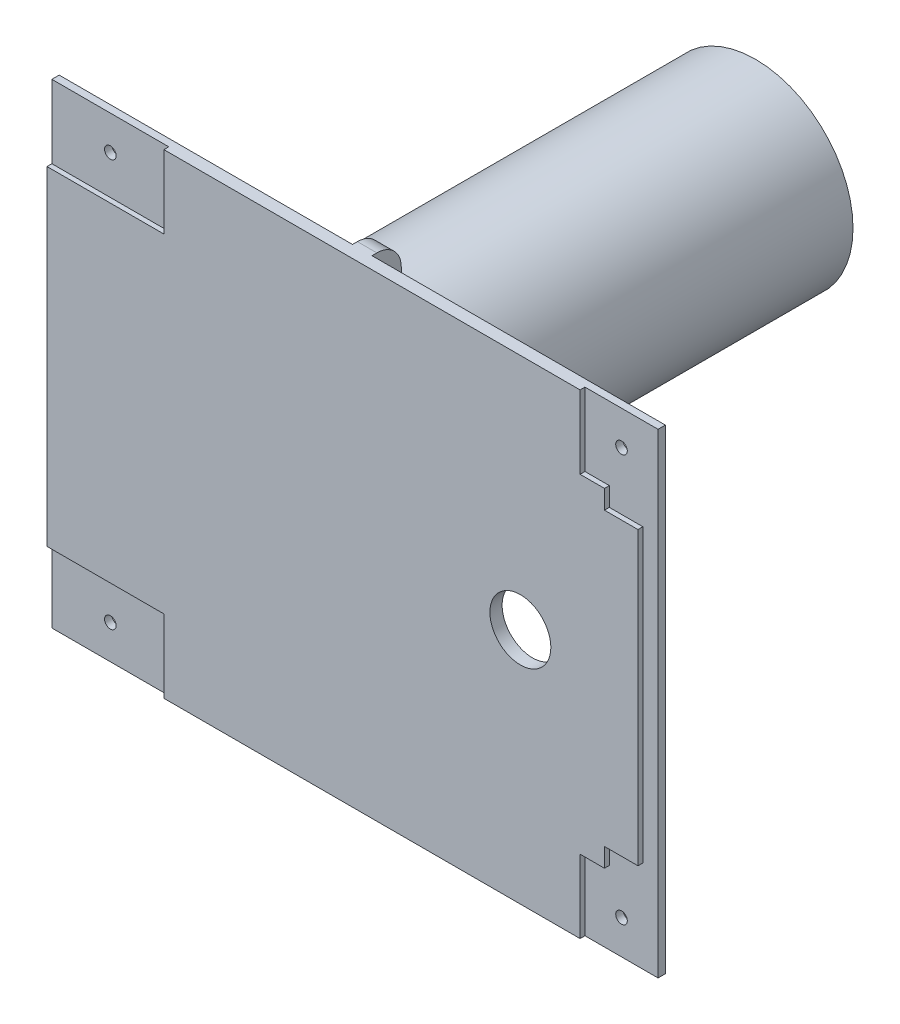
SolidWorks part; units mm, degrees
ref_plane "Alzado" through (0, 0, 0) normal (0, 0, 1) x (1, 0, 0)
ref_plane "Planta" through (0, 0, 0) normal (0, 1, 0) x (1, 0, 0)
ref_plane "Vista lateral" through (0, 0, 0) normal (1, 0, 0) x (0, 0, -1)
sketch "Croquis1" plane through (0, 0, 0) normal (0, 0, 1) x (1, 0, 0)
  line L1 (-117.2917, 97.7627) -> (131.4683, 97.7627)
  line L2 (-117.2917, 97.7627) -> (-117.2917, -97.2373)
  line L3 (-117.2917, -97.2373) -> (131.4683, -97.2373)
  line L4 (131.4683, 97.7627) -> (131.4683, -97.2373)
  dimension "D1" = 248.76
  dimension "D2" = 195
extrude "Saliente-Extruir1" add sketch "Croquis1" along normal blind 5
sketch "Croquis2" plane through (0, 0, 5) normal (0, 0, 1) x (1, 0, 0)
  line L0 (-117.2917, 0.2627) -> (131.4683, 0.2627) construction
  line L1 (-117.2917, 97.7627) -> (-117.2917, -97.2373) construction
  line L2 (131.4683, -97.2373) -> (131.4683, 97.7627) construction
  line L3 (-117.2917, -97.2373) -> (-69.2917, -97.2373)
  line L4 (-117.2917, -97.2373) -> (131.4683, -97.2373) construction
  line L5 (-69.2917, -97.2373) -> (-69.2917, -67.2373)
  line L6 (-69.2917, -67.2373) -> (-117.2917, -67.2373)
  line L7 (-117.2917, -67.2373) -> (-117.2917, -97.2373)
  line L8 (131.4683, 67.7627) -> (101.4683, 67.7627)
  line L9 (131.4683, -97.2373) -> (101.4683, -97.2373)
  line L10 (131.4683, -97.2373) -> (131.4683, -67.2373)
  line L11 (131.4683, -67.2373) -> (101.4683, -67.2373)
  line L12 (101.4683, -97.2373) -> (101.4683, -67.2373)
  line L13 (101.4683, 97.7627) -> (101.4683, 67.7627)
  line L14 (131.4683, 97.7627) -> (101.4683, 97.7627)
  line L15 (131.4683, 97.7627) -> (131.4683, 67.7627)
  line L16 (-69.2917, 67.7627) -> (-117.2917, 67.7627)
  line L17 (-69.2917, 97.7627) -> (-69.2917, 67.7627)
  line L18 (-117.2917, 97.7627) -> (-69.2917, 97.7627)
  line L19 (-117.2917, 67.7627) -> (-117.2917, 97.7627)
  dimension "D1" = 48
  dimension "D2" = 30
  dimension "D3" = 30
  dimension "D4" = 30
extrude "Cortar-Extruir1" cut sketch "Croquis2" against normal blind 2
sketch "Croquis3" plane through (0, 0, 5) normal (0, 0, 1) x (1, 0, 0)
  line L0 (-69.2917, 97.7627) -> (-117.2917, 97.7627) construction
  line L1 (116.4683, 83.7627) -> (116.4683, 67.7627) construction
  line L3 (116.4683, -83.2373) -> (116.4683, -67.2373) construction
  line L5 (131.4683, -67.2373) -> (101.4683, -67.2373) construction
  line L6 (101.4683, 67.7627) -> (131.4683, 67.7627) construction
  line L7 (-93.2917, 83.7627) -> (-93.2917, 67.7627) construction
  line L8 (-117.2917, 67.7627) -> (-69.2917, 67.7627) construction
  line L9 (-93.2917, -83.2373) -> (-93.2917, -67.2373) construction
  line L10 (-69.2917, -67.2373) -> (-117.2917, -67.2373) construction
  circle A0 centre (-93.2917, 83.7627) radius 2.375
  circle A1 centre (-93.2917, -83.2373) radius 2.375
  circle A2 centre (116.4683, 83.7627) radius 2.375
  circle A3 centre (116.4683, -83.2373) radius 2.375
  dimension "D2" = 4.75
  dimension "D3" = 4.75
  dimension "D5" = 4.75
  dimension "D6" = 4.75
  dimension "D1" = 14
  dimension "D4" = 14
  dimension "D7" = 209.76
  dimension "D8" = 16
  dimension "D9" = 16
extrude "Cortar-Extruir2" cut sketch "Croquis3" against normal blind 10
sketch "Croquis4" plane through (0, 0, 0) normal (0, 0, -1) x (-1, 0, 0)
  line L5 (-131.4683, -97.2373) -> (-131.4683, 97.7627) construction
  line L7 (-131.4683, 97.7627) -> (117.2917, 97.7627) construction
  circle A0 centre (37.5317, 0.2627) radius 40
  dimension "D3" = 80
  dimension "D1" = 169
  dimension "D2" = 97.5
extrude "Saliente-Extruir2" add sketch "Croquis4" along normal blind 206 contours A0
sketch "Croquis5" plane through (0, 0, 0) normal (0, 0, -1) x (-1, 0, 0)
  line L0 (-131.4683, 0.2627) -> (117.2917, 0.2627) construction
  line L1 (-131.4683, -97.2373) -> (-131.4683, 97.7627) construction
  line L2 (117.2917, 97.7627) -> (117.2917, -97.2373) construction
  circle A0 centre (-76.9683, 0.2627) radius 12.5
  dimension "D1" = 25
  dimension "D2" = 54.5
extrude "Cortar-Extruir3" cut sketch "Croquis5" against normal blind 10
sketch "Croquis6" plane through (0, 0, 0) normal (0, 0, -1) x (-1, 0, 0)
  line L0 (-131.4683, 97.7627) -> (117.2917, 97.7627) construction
  line L1 (-7.0883, 97.7627) -> (-7.0883, -97.2373)
  line L2 (117.2917, -97.2373) -> (-131.4683, -97.2373) construction
  line L3 (-7.0883, 97.7627) -> (117.2917, 97.7627)
  line L4 (117.2917, 97.7627) -> (117.2917, -97.2373)
  line L5 (117.2917, -97.2373) -> (-7.0883, -97.2373)
  line L6 (-131.4683, 0.2627) -> (56.0317, 0.2627)
  line L7 (-131.4683, -97.2373) -> (-131.4683, 97.7627) construction
  circle A1 centre (56.0317, 0.2627) radius 100
  dimension "D1" = 200
  dimension "D2" = 187.5
sketch "Croquis9" plane through (0, 97.7627, 0) normal (0, 1, 0) x (1, 0, 0)
  line L0 (7.0883, 0) -> (7.0883, -5)
  line L1 (131.4683, 0) -> (-117.2917, 0) construction
  line L2 (101.4683, -5) -> (-69.2917, -5) construction
ref_plane "Plano3" through (7.0883, 0, 0) normal (1, 0, 0) x (0, 0, -1)
sketch "Croquis12" plane through (7.0883, 0, 0) normal (1, 0, 0) x (0, 0, -1)
  line L0 (0, 97.7627) -> (0, 67.7627)
  line L1 (0, 67.7627) -> (12, 67.7627)
  line L2 (12, 67.7627) -> (12, 97.7627)
  line L3 (12, 97.7627) -> (0, 97.7627)
  line L4 (0, -97.2373) -> (12, -97.2373)
  line L5 (12, -97.2373) -> (12, -67.2373)
  line L6 (12, -67.2373) -> (0, -67.2373)
  line L7 (0, -67.2373) -> (0, -97.2373)
  dimension "D1" = 30
  dimension "D2" = 12
  dimension "D3" = 30
  dimension "D4" = 12
extrude "Saliente-Extruir3" add sketch "Croquis12" along normal mid plane 8
fillet "Redondeo1" radius 10 2 edges at (7.0883, -67.2373, 0) (7.0883, 67.7627, 0)
fillet "Redondeo2" radius 10 2 edges at (7.0883, 67.7627, -12) (7.0883, -67.2373, -12)
fillet "Redondeo3" radius 10 2 edges at (7.0883, -97.2373, -12) (7.0883, 97.7627, -12)
sketch "Croquis13" plane through (11.0883, 0, 0) normal (1, 0, 0) x (0, 0, -1)
  line L0 (-5, 0.2627) -> (206, 0.2627) construction
  line L1 (-5, -67.2373) -> (-5, 67.7627) construction
  line L2 (206, -39.7373) -> (206, 40.2627) construction
  line L3 (6, 87.7627) -> (12, 87.7627) construction
  line L4 (6, 87.7627) -> (6, 77.7627) construction
  circle A0 centre (6, 87.7627) radius 1.625
  circle A1 centre (6, 77.7627) radius 1.625
  circle A2 centre (6, -77.2373) radius 1.625
  circle A3 centre (6, -87.2373) radius 1.625
  dimension "D3" = 3.25
  dimension "D4" = 3.25
  dimension "D1" = 6
extrude "Cortar-Extruir5" cut sketch "Croquis13" against normal through all both and the other way through all
sketch "Croquis14" plane through (0, 0, 0) normal (0, 0, -1) x (-1, 0, 0)
  line L0 (-7.0883, 97.7627) -> (-7.0883, -97.2373)
  line L1 (-7.0883, 97.7627) -> (117.2917, 97.7627)
  line L2 (117.2917, 97.7627) -> (117.2917, -97.2373)
  line L3 (117.2917, -97.2373) -> (-7.0883, -97.2373)
sketch "Croquis15" plane through (0, 0, 5) normal (0, 0, 1) x (1, 0, 0)
  line L0 (111.4683, 67.7627) -> (131.4683, 67.7627)
  line L1 (111.4683, 67.7627) -> (111.4683, 60.0127)
  line L2 (131.4683, -67.2373) -> (101.4683, -67.2373) construction
  line L3 (111.4683, -67.2373) -> (111.4683, -59.4873)
  line L4 (111.4683, -59.4873) -> (125.2183, -59.4873)
  line L5 (125.2183, -59.4873) -> (125.2183, 60.0127)
  line L6 (111.4683, 60.0127) -> (125.2183, 60.0127)
  line L7 (111.4683, -67.2373) -> (131.4683, -67.2373)
  line L10 (131.4683, -67.2373) -> (131.4683, 67.7627)
  dimension "D1" = 119.5
  dimension "D2" = 7.75
  dimension "D3" = 13.75
extrude "Cortar-Extruir7" cut sketch "Croquis15" against normal blind 2
